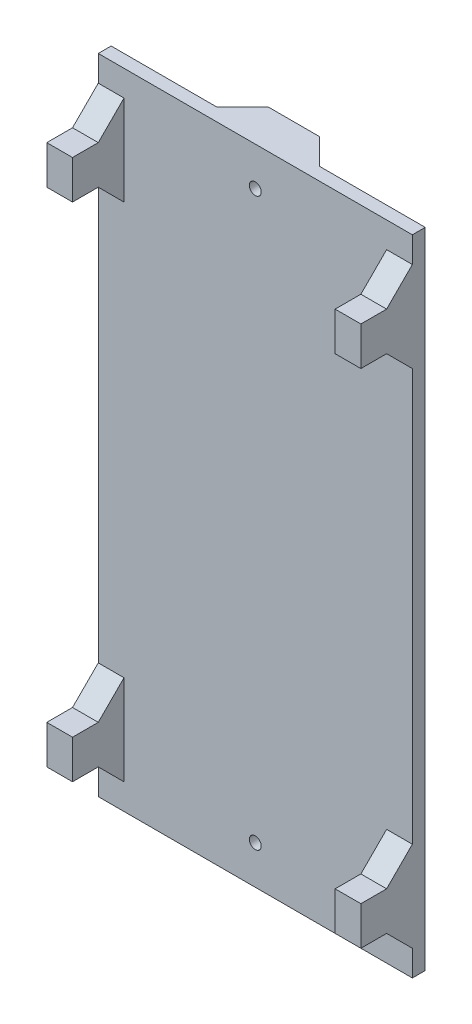
SolidWorks part; units mm, degrees
ref_plane "Front Plane" through (0, 0, 0) normal (0, 0, 1) x (1, 0, 0)
ref_plane "Top Plane" through (0, 0, 0) normal (0, 1, 0) x (1, 0, 0)
ref_plane "Right Plane" through (0, 0, 0) normal (1, 0, 0) x (0, 0, -1)
sketch "Sketch1" plane through (0, 0, 0) normal (0, 0, 1) x (1, 0, 0)
  line L1 (-61, -125) -> (61, -125)
  line L2 (-61, -125) -> (-61, 125)
  line L3 (-61, 125) -> (61, 125)
  line L4 (61, -125) -> (61, 125)
  line L5 (-61, -125) -> (61, 125) construction
  line L6 (-61, 125) -> (61, -125) construction
  point P0 (0, 0)
  dimension "D1" = 122
  dimension "D2" = 250
extrude "Boss-Extrude1" add sketch "Sketch1" along normal blind 5
sketch "Sketch9" plane through (0, 125, 0) normal (0, 1, 0) x (1, 0, 0)
  line L5 (-10, 10) -> (10, 10)
  line L6 (-20, 0) -> (-10, 10)
  line L7 (61, 0) -> (-61, 0) construction
  line L8 (-20, 0) -> (20, 0)
  line L9 (20, 0) -> (10, 10)
  point P11 (0, 10)
  dimension "D1" = 45
  dimension "D2" = 45
  dimension "D3" = 10
  dimension "D4" = 20
extrude "Boss-Extrude7" add sketch "Sketch9" against normal up to surface (250 mm away) up to face at (0, -125, 2.5)
sketch "Sketch2" plane through (0, 0, 0) normal (0, 0, 1) x (1, 0, 0)
  line L0 (61, 125) -> (-61, 125) construction
  line L1 (-61, -125) -> (61, -125) construction
  circle A0 centre (0, 110) radius 2.3
  circle A1 centre (0, -110) radius 2.3
  dimension "D1" = 4.6
  dimension "D2" = 15
  dimension "D3" = 15
extrude "Cut-Extrude2" cut sketch "Sketch2" along normal through all both and the other way through all
sketch "Sketch10" plane through (0, 0, 5) normal (0, 0, 1) x (1, 0, 0)
  line L0 (-61, 125) -> (-61, -125) construction
  line L9 (-61, -105) -> (-51, -105)
  line L10 (-61, -105) -> (-61, -90)
  line L11 (-61, -90) -> (-51, -90)
  line L12 (-51, -105) -> (-51, -90)
  line L13 (61, -125) -> (61, 125) construction
  line L14 (61, -90) -> (51, -90)
  line L15 (61, -90) -> (61, -105)
  line L16 (61, -105) -> (51, -105)
  line L17 (51, -90) -> (51, -105)
  line L18 (61, 125) -> (-61, 125) construction
  line L19 (-61, 105) -> (-51, 105)
  line L20 (-61, 105) -> (-61, 90)
  line L21 (-61, 90) -> (-51, 90)
  line L22 (-51, 105) -> (-51, 90)
  line L23 (61, 105) -> (51, 105)
  line L24 (61, 105) -> (61, 90)
  line L25 (61, 90) -> (51, 90)
  line L26 (51, 105) -> (51, 90)
  line L27 (-61, -125) -> (61, -125) construction
  dimension "D1" = 10
  dimension "D2" = 20
  dimension "D3" = 15
  dimension "D4" = 20
extrude "Boss-Extrude8" add sketch "Sketch10" along normal blind 20
chamfer "Chamfer1" distance 10 angle 45 8 edges at (56, -90, 5) (56, -105, 5) (-56, -105, 5) (-56, -90, 5) (-56, 90, 5) (56, 90, 5) (56, 105, 5) (-56, 105, 5)
